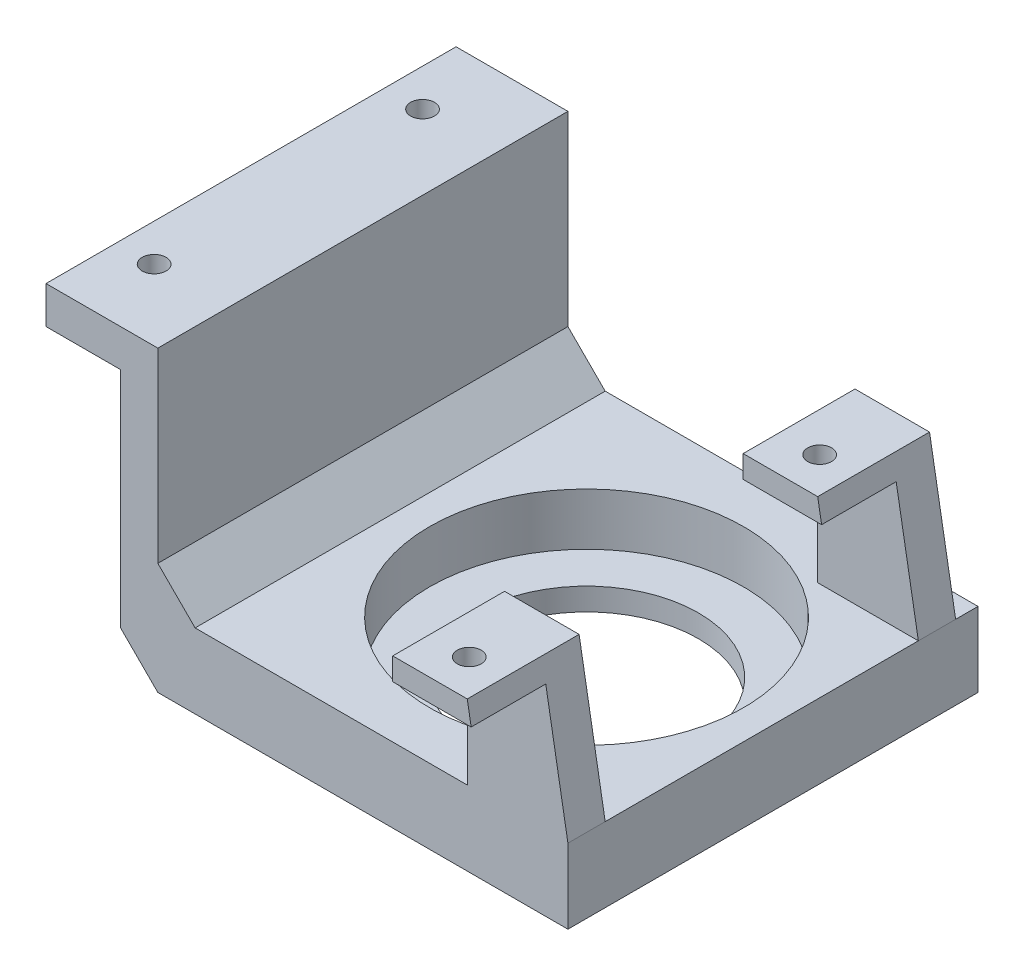
SolidWorks part; units mm, degrees
ref_plane "Alzado" through (0, 0, 0) normal (0, 0, 1) x (1, 0, 0)
ref_plane "Planta" through (0, 0, 0) normal (0, 1, 0) x (1, 0, 0)
ref_plane "Vista lateral" through (0, 0, 0) normal (1, 0, 0) x (0, 0, -1)
ref_plane "Plano1" through (0, 25, 0) normal (0, 1, 0) x (1, 0, 0)
sketch "Croquis4" plane through (0, 0, 0) normal (0, 0, 1) x (1, 0, 0)
  line L0 (-30, 5) -> (-30, 30)
  line L5 (-25, 5) -> (30, 5)
  line L6 (-30, 5) -> (-30, -5)
  line L7 (-30, -5) -> (30, -5)
  line L8 (30, 5) -> (30, -5)
  line L9 (-30, 5) -> (30, -5) construction
  line L10 (-30, -5) -> (30, 5) construction
  line L11 (-30, 30) -> (-40, 30)
  line L12 (-40, 30) -> (-40, 35)
  line L13 (-40, 35) -> (-25, 35)
  line L14 (-25, 35) -> (-25, 5)
  point P0 (0, 0)
  dimension "D1" = 10
  dimension "D2" = 60
  dimension "D3" = 5
  dimension "D4" = 5
  dimension "D5" = 10
  dimension "D6" = 10
  dimension "D7" = 30
extrude "Saliente-Extruir2" add sketch "Croquis4" along normal blind 55
sketch "Croquis6" plane through (0, 5, 0) normal (0, 1, 0) x (1, 0, 0)
  line L1 (30, -55) -> (30, 0) construction
  line L2 (30, -27.5) -> (-25, -27.5) construction
  line L3 (-25, -55) -> (-25, 0) construction
  circle A0 centre (5, -27.5) radius 21.05
  dimension "D1" = 42.1
  dimension "D3" = 25
extrude "Cortar-Extruir1" cut sketch "Croquis6" against normal blind 7
sketch "Croquis8" plane through (0, -2, 0) normal (0, 1, 0) x (1, 0, 0)
  circle A0 centre (5, -27.5) radius 15
  dimension "D1" = 30
extrude "Cortar-Extruir2" cut sketch "Croquis8" against normal through all both and the other way through all
sketch "Croquis9" plane through (0, 30, 0) normal (0, -1, 0) x (1, 0, 0)
  line L0 (-40, 27.5) -> (-30, 27.5) construction
  line L1 (-40, 55) -> (-40, 0) construction
  line L2 (-30, 55) -> (-30, 0) construction
  line L3 (-35, 27.5) -> (-35, 61.1151) construction
  circle A0 centre (-35, 45.5) radius 1.6
  circle A2 centre (-35, 9.5) radius 1.6
  dimension "D1" = 18
  dimension "D2" = 3.2
extrude "Cortar-Extruir3" cut sketch "Croquis9" against normal through all both and the other way through all
chamfer "Chaflán1" distance 5 angle 45 2 edges at (-25, 5, 27.5) (-30, -5, 27.5)
sketch "Croquis11" plane through (0, 5, 0) normal (0, 1, 0) x (1, 0, 0)
  line L1 (30, -55) -> (30, 0) construction
  line L4 (26.5, -55) -> (26.5, -40.1993) construction
  line L6 (30, -27.5) -> (-20, -27.5) construction
  line L7 (-20, 0) -> (-20, -55) construction
  line L12 (26.5, -55) -> (26.5, -50)
  line L13 (30, -55) -> (-20, -55) construction
  line L14 (26.5, -50) -> (16.5, -50)
  line L15 (16.5, -50) -> (16.5, -55)
  line L16 (16.5, -55) -> (26.5, -55)
  line L17 (26.5, -9) -> (26.5, -66) construction
  dimension "D1" = 10
  dimension "D2" = 5
extrude "Saliente-Extruir3" add sketch "Croquis11" along normal blind 20
sketch "Croquis13" plane through (0, 5, 0) normal (0, 1, 0) x (1, 0, 0)
  line L0 (26.5, -8) -> (26.5, -3)
  line L1 (26.5, -3) -> (16.5, -3)
  line L2 (16.5, -3) -> (16.5, -8)
  line L3 (16.5, -8) -> (26.5, -8)
  line L4 (26.5, -9) -> (26.5, 2.2982) construction
  line L5 (26.5, -9) -> (-5.5, -9) construction
  dimension "D1" = 5
  dimension "D2" = 10
  dimension "D3" = 1
extrude "Saliente-Extruir5" add sketch "Croquis13" along normal blind 20
sketch "Croquis16" plane through (0, 0, 55) normal (0, 0, 1) x (1, 0, 0)
  line L0 (30, 5) -> (26.5, 25)
  line L1 (26.5, 25) -> (26.5, 5)
  line L2 (26.5, 5) -> (30, 5)
  point P4 (26.5, 25)
extrude "Saliente-Extruir7" add sketch "Croquis16" against normal blind 5
sketch "Croquis17" plane through (0, 0, 8) normal (0, 0, 1) x (1, 0, 0)
  line L0 (30, 5) -> (26.5, 25)
  line L1 (26.5, 25) -> (26.5, 5)
  line L2 (26.5, 5) -> (30, 5)
  point P4 (26.5, 25)
extrude "Saliente-Extruir8" add sketch "Croquis17" against normal blind 5
sketch "Croquis19" plane through (0, 0, 55) normal (0, 0, 1) x (1, 0, 0)
  line L0 (16.5, 25) -> (16.5, 22)
  line L1 (16.5, 25) -> (16.5, 5) construction
  line L2 (16.5, 22) -> (27.025, 22)
  line L3 (30, 5) -> (26.5, 25) construction
  line L4 (27.025, 22) -> (26.5, 25)
  line L5 (26.5, 25) -> (16.5, 25)
  point P5 (18.2496, 24.1859)
  dimension "D1" = 3
extrude "Saliente-Extruir9" add sketch "Croquis19" along normal blind 10
sketch "Croquis20" plane through (0, 0, 8) normal (0, 0, 1) x (1, 0, 0)
  line L0 (16.5, 25) -> (16.5, 22)
  line L1 (16.5, 22) -> (27.025, 22)
  line L2 (27.025, 22) -> (26.5, 25)
  line L3 (26.5, 25) -> (16.5, 25)
extrude "Saliente-Extruir10" add sketch "Croquis20" along normal blind 10
sketch "Croquis15" plane through (0, 22, 0) normal (0, -1, 0) x (1, 0, 0)
  line L0 (21.7625, 65) -> (21.7625, 8) construction
  line L3 (27.025, 60) -> (21.7625, 60) construction
  line L5 (27.025, 13) -> (16.5, 13) construction
  line L8 (16.5, 65) -> (27.025, 65) construction
  line L9 (27.025, 65) -> (27.025, 55) construction
  line L10 (27.025, 18) -> (27.025, 8) construction
  line L11 (16.5, 8) -> (27.025, 8) construction
  line L12 (16.5, 18) -> (16.5, 8) construction
  circle A0 centre (21.7625, 60) radius 1.6
  circle A1 centre (21.7625, 13) radius 1.6
  point P2 (21.5285, 65)
  point P5 (21.7625, 65)
  point P8 (27.025, 60)
  point P14 (27.025, 13)
  point P19 (21.7625, 8)
  point P22 (22.1303, 13)
  point P23 (16.5, 13)
  dimension "D1" = 3.2
extrude "Cortar-Extruir4" cut sketch "Croquis15" against normal through all
